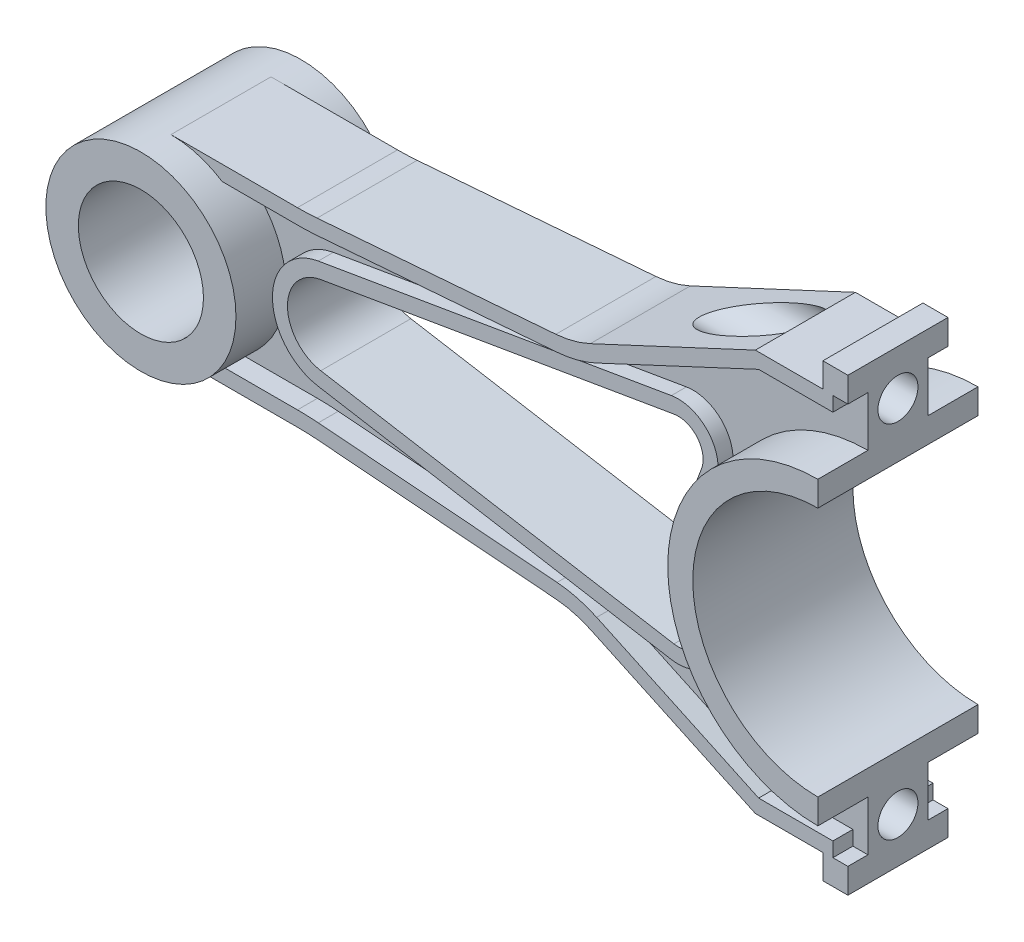
SolidWorks part; units mm, degrees
ref_plane "Front Plane" through (0, 0, 0) normal (0, 0, 1) x (1, 0, 0)
ref_plane "Top Plane" through (0, 0, 0) normal (0, 1, 0) x (1, 0, 0)
ref_plane "Right Plane" through (0, 0, 0) normal (1, 0, 0) x (0, 0, -1)
sketch "Sketch1" plane through (0, 0, 0) normal (0, 0, 1) x (1, 0, 0)
  line L0 (0, 0) -> (-97, 0) construction
  line L1 (-135.29, 19) -> (-110.0045, 19)
  line L2 (-106.0816, 19.1541) -> (-58.3615, 22.9098)
  line L3 (0, 45) -> (-5, 45)
  line L4 (-5, 45) -> (-5, 40.1)
  line L5 (-5, 40.1) -> (-18.5, 40.1)
  line L6 (-18.5, 40.1) -> (-51.4783, 24.722)
  line L7 (0, 45) -> (0, 25)
  line L8 (0, -45) -> (0, -25)
  line L9 (0, -45) -> (-5, -45)
  line L10 (-5, -45) -> (-5, -40.1)
  line L11 (-5, -40.1) -> (-18.5, -40.1)
  line L12 (-18.5, -40.1) -> (-51.4783, -24.722)
  line L13 (-106.0816, -19.1541) -> (-58.3615, -22.9098)
  line L14 (-135.29, -19) -> (-110.0045, -19)
  line L15 (-106.341, 7.8868) -> (-35.7708, 19.8862)
  line L16 (-106.341, -7.8868) -> (-35.7708, -19.8862)
  line L17 (-113, 0) -> (-135.29, 0) construction
  circle A0 centre (-135.29, 0) radius 19
  circle A1 centre (-135.29, 0) radius 12.5
  arc A2 (-106.341, 7.8868) -> (-106.341, -7.8868) centre (-105, 0) ccw
  arc A3 (-30.3362, 12.9889) -> (-30.3362, -12.9889) centre (0, 0) ccw
  arc A4 (0, 30) -> (0, -30) centre (0, 0) ccw
  arc A5 (0, 25) -> (0, -25) centre (0, 0) ccw
  arc A6 (-51.4783, -24.722) -> (-58.3615, -22.9098) centre (-59.9306, -42.8481) ccw
  arc A7 (-58.3615, 22.9098) -> (-51.4783, 24.722) centre (-59.9306, 42.8481) ccw
  arc A8 (-106.0816, -19.1541) -> (-110.0045, -19) centre (-110.0045, -69) ccw
  arc A9 (-110.0045, 19) -> (-106.0816, 19.1541) centre (-110.0045, 69) ccw
  arc A10 (-30.3362, 12.9889) -> (-35.7708, 19.8862) centre (-34.9326, 14.957) ccw
  arc A11 (-30.3362, -12.9889) -> (-35.7708, -19.8862) centre (-34.9326, -14.957) cw
  point P28 (-54.756, -23.1935)
  point P31 (-54.756, 23.1935)
  point P34 (-108.04, -19)
  point P37 (-108.04, 19)
  dimension "D2" = 38
  dimension "D3" = 25
  dimension "D4" = 16
  dimension "D6" = 66
  dimension "D7" = 60
  dimension "D8" = 50
  dimension "D16" = 20
  dimension "D17" = 50
  dimension "D19" = 5
  dimension "D20" = 5
  dimension "D1" = 135.29
  dimension "D5" = 30.29
  dimension "D9" = 20
  dimension "D10" = 5
  dimension "D11" = 13.5
  dimension "D12" = 4.9
  dimension "D13" = 27.25
  dimension "D14" = 9
  dimension "D15" = 155
  dimension "D18" = 19.3
extrude "Boss-Extrude1" add sketch "Sketch1" along normal mid plane 12 contours A0 A1 | A9 L1 A0 L14 A8 L13 A6 L12 L11 L10 L9 L8 A4 L7 L3 L4 L5 L6 A7 L2 A3 A11 L16 A2 L15 A10 | A5 L7 A4 L8 region at (-122.6473, 17.3751, 0) region at (-122.235, 13.055, 0) region at (-0.6708, 27.5, 0)
extrude "Boss-Extrude2" add sketch "Sketch1<4>" along normal mid plane 32 contours A0 A1 | A5 L7 A4 L8 region at (-122.235, 13.055, 0) region at (-0.6708, 27.5, 0)
sketch "Sketch1<4>" plane through (0, 0, 0) normal (0, 0, 1) x (1, 0, 0) same geometry as "Sketch1"
sketch "Sketch2" plane through (0, 0, 0) normal (0, 0, 1) x (1, 0, 0)
  line L0 (-5, 45) -> (-5, 40.1) construction
  line L1 (0, 45) -> (-5, 45) construction
  line L2 (-5, 40.1) -> (-18.5, 40.1) construction
  line L3 (-18.5, 40.1) -> (-51.4783, 24.722) construction
  line L4 (-106.0816, 19.1541) -> (-58.3615, 22.9098) construction
  line L5 (-135.29, 19) -> (-110.0045, 19) construction
  line L6 (-5, 45) -> (-5, 40.1)
  line L7 (0, 45) -> (-5, 45)
  line L8 (-5, 40.1) -> (-18.5, 40.1)
  line L9 (-18.5, 40.1) -> (-51.4783, 24.722)
  line L10 (-106.0816, 19.1541) -> (-58.3615, 22.9098)
  line L11 (-135.29, 19) -> (-110.0045, 19)
  line L12 (-125.043, 16) -> (-110.0045, 16)
  line L13 (-105.8462, 16.1634) -> (-58.1261, 19.919)
  line L14 (-17.8349, 37.1) -> (-50.2104, 22.0031)
  line L15 (0, 40) -> (-3, 40)
  line L16 (0, 45) -> (0, 30) construction
  line L17 (-3, 40) -> (-3, 37.1)
  line L18 (0, 42) -> (-2, 42) construction
  line L19 (-2, 42) -> (-2, 37.1) construction
  line L20 (-2, 37.1) -> (-17.8349, 37.1) construction
  line L21 (-3, 37.1) -> (-17.8349, 37.1)
  line L22 (-135.29, 16) -> (-110.0045, 16) construction
  line L23 (0, 0) -> (-187.7615, 0) construction
  line L24 (0, -40) -> (-3, -40)
  line L25 (-3, -40) -> (-3, -37.1)
  line L26 (-3, -37.1) -> (-17.8349, -37.1)
  line L27 (-17.8349, -37.1) -> (-50.2104, -22.0031)
  line L28 (-105.8462, -16.1634) -> (-58.1261, -19.919)
  line L29 (-125.043, -16) -> (-110.0045, -16)
  line L30 (0, 45) -> (0, 40)
  line L31 (0, -45) -> (0, -40)
  line L32 (0, -45) -> (-5, -45)
  line L33 (-5, -45) -> (-5, -40.1)
  line L34 (-5, -40.1) -> (-18.5, -40.1)
  line L35 (-18.5, -40.1) -> (-51.4783, -24.722)
  line L36 (-106.0816, -19.1541) -> (-58.3615, -22.9098)
  line L37 (-135.29, -19) -> (-110.0045, -19)
  arc A0 (-58.3615, 22.9098) -> (-51.4783, 24.722) centre (-59.9306, 42.8481) ccw construction
  arc A1 (-110.0045, 19) -> (-106.0816, 19.1541) centre (-110.0045, 69) ccw construction
  arc A2 (-58.3615, 22.9098) -> (-51.4783, 24.722) centre (-59.9306, 42.8481) ccw
  arc A3 (-110.0045, 19) -> (-106.0816, 19.1541) centre (-110.0045, 69) ccw
  arc A4 (-110.0045, 16) -> (-105.8462, 16.1634) centre (-110.0045, 69) ccw
  circle A5 centre (-135.29, 0) radius 19
  arc A6 (-135.29, -19) -> (-125.043, -16) centre (-135.29, 0) ccw
  arc A7 (-58.1261, 19.919) -> (-50.2104, 22.0031) centre (-59.9306, 42.8481) ccw
  arc A8 (-58.1261, -19.919) -> (-50.2104, -22.0031) centre (-59.9306, -42.8481) cw
  arc A9 (-110.0045, -16) -> (-105.8462, -16.1634) centre (-110.0045, -69) cw
  arc A10 (-125.043, 16) -> (-135.29, 19) centre (-135.29, 0) ccw
  arc A11 (-58.3615, -22.9098) -> (-51.4783, -24.722) centre (-59.9306, -42.8481) cw
  arc A12 (-110.0045, -19) -> (-106.0816, -19.1541) centre (-110.0045, -69) cw
  dimension "D3" = 5
  dimension "D4" = 3
  dimension "D1" = 0
  dimension "D2" = 3
extrude "Boss-Extrude3" add sketch "Sketch2" along normal mid plane 20
sketch "Sketch3" plane through (0, 0, 0) normal (1, 0, 0) x (0, 0, -1)
  line L0 (-10, -45) -> (10, -45) construction
  line L3 (0, -45) -> (0, -36) construction
  circle A0 centre (0, -36) radius 4
  dimension "D1" = 8
  dimension "D2" = 9
extrude "Cut-Extrude2" cut sketch "Sketch3" against normal blind 18.5
sketch "Sketch4" plane through (-18.5, 0, 0) normal (1, 0, 0) x (0, 0, -1)
  circle A0 centre (0, -36) radius 5.795
  dimension "D1" = 11.59
extrude "Cut-Extrude4" cut sketch "Sketch4" against normal through all
mirror "Mirror1" about plane through (0, 0, 0) normal (0, 1, 0) of "Cut-Extrude2", "Cut-Extrude4"
sketch "Sketch5" plane through (0, 0, 0) normal (0, 0, 1) x (1, 0, 0)
  line L0 (-106.341, 7.8868) -> (-35.7708, 19.8862) construction
  line L1 (-106.341, -7.8868) -> (-35.7708, -19.8862) construction
  line L2 (-106.341, -7.8868) -> (-35.7708, -19.8862)
  line L3 (-106.341, 7.8868) -> (-35.7708, 19.8862)
  line L4 (-106.8439, 10.8444) -> (-36.2737, 22.8438)
  line L5 (-106.8439, -10.8444) -> (-36.2737, -22.8438)
  arc A0 (-30.3362, 12.9889) -> (-35.7708, 19.8862) centre (-34.9326, 14.957) ccw construction
  arc A1 (-30.3362, 12.9889) -> (-30.3362, -12.9889) centre (0, 0) ccw construction
  arc A2 (-35.7708, -19.8862) -> (-30.3362, -12.9889) centre (-34.9326, -14.957) ccw construction
  arc A3 (-106.341, 7.8868) -> (-106.341, -7.8868) centre (-105, 0) ccw construction
  arc A4 (-30.3362, 12.9889) -> (-35.7708, 19.8862) centre (-34.9326, 14.957) ccw
  arc A5 (-30.3362, 12.9889) -> (-30.3362, -12.9889) centre (0, 0) ccw
  arc A6 (-35.7708, -19.8862) -> (-30.3362, -12.9889) centre (-34.9326, -14.957) ccw
  arc A7 (-106.341, 7.8868) -> (-106.341, -7.8868) centre (-105, 0) ccw
  arc A8 (-27.5784, 11.8081) -> (-36.2737, 22.8438) centre (-34.9326, 14.957) ccw
  arc A9 (-27.5784, 11.8081) -> (-27.5784, -11.8081) centre (0, 0) ccw
  arc A10 (-36.2737, -22.8438) -> (-27.5784, -11.8081) centre (-34.9326, -14.957) ccw
  arc A11 (-106.8439, 10.8444) -> (-106.8439, -10.8444) centre (-105, 0) ccw
  dimension "D1" = 3
extrude "Boss-Extrude4" add sketch "Sketch5" along normal mid plane 18
